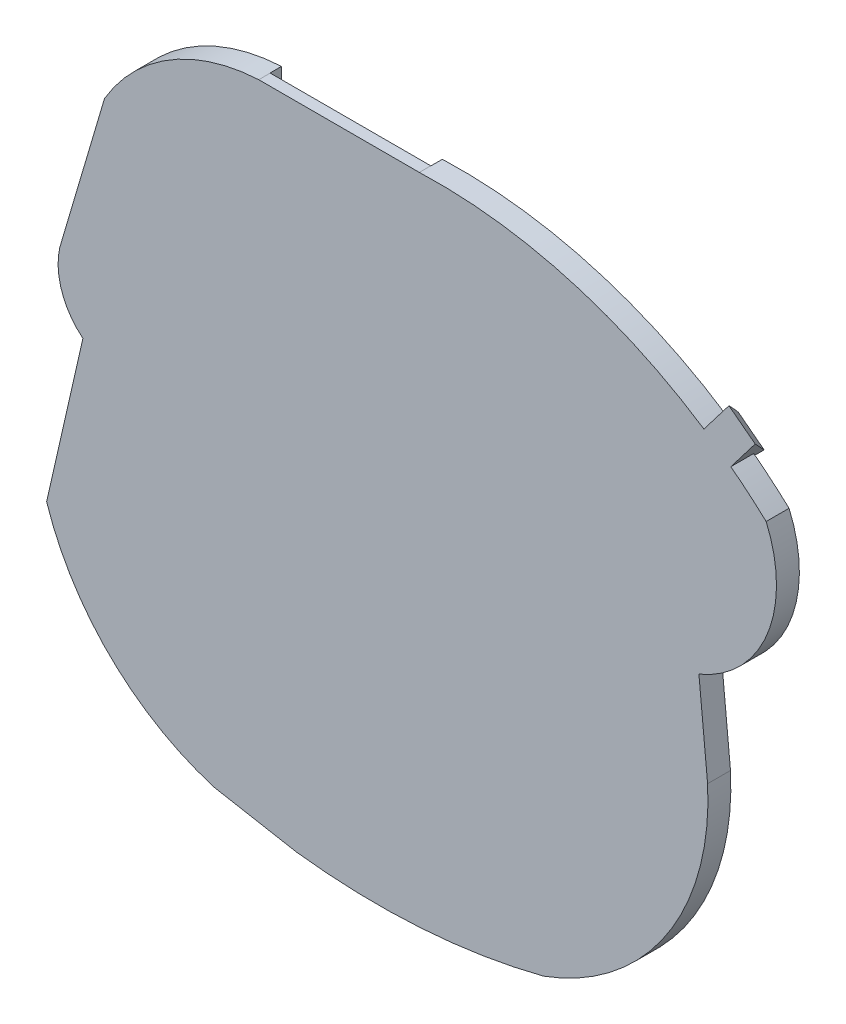
SolidWorks part; units mm, degrees
ref_plane "Front Plane" through (0, 0, 0) normal (0, 0, 1) x (1, 0, 0)
ref_plane "Top Plane" through (0, 0, 0) normal (0, 1, 0) x (1, 0, 0)
ref_plane "Right Plane" through (0, 0, 0) normal (1, 0, 0) x (0, 0, -1)
sketch "Sketch1" plane through (0, 0, 0) normal (0, 0, 1) x (1, 0, 0)
  line L0 (-85.5336, -305.9757) -> (-99.8837, -303.3682)
  line L2 (-13.742, -259.6992) -> (-15.2594, -243.8824)
  line L3 (-92.1446, -194.3927) -> (-64.0896, -194.3913)
  line L15 (-119.1233, -208.6879) -> (-126.5485, -233.818)
  line L20 (-129.2393, -274.7737) -> (-122.901, -246.8902)
  line L38 (-85.5336, -305.9757) -> (-85.5336, -305.9816)
  line L40 (-64.114, -192.3791) -> (-92.1689, -192.3791)
  line L44 (-64.0896, -194.3913) -> (-64.0896, -196.3927)
  line L45 (-19.5312, -241.5935) -> (-17.6923, -260.2487)
  line L46 (-125.176, -275.0633) -> (-119.3965, -249.6382)
  line L47 (-119.3965, -249.6382) -> (-118.0843, -245.1972)
  line L48 (-118.0843, -245.1972) -> (-118.3529, -245.047)
  line L49 (-122.5408, -235.0791) -> (-115.4629, -210.4053)
  line L50 (-92.1446, -196.3927) -> (-92.1446, -194.3927)
  line L51 (-92.1446, -194.3927) -> (-92.2026, -194.3927)
  line L52 (-117.3122, -209.5987) -> (-124.4351, -234.4295)
  line L53 (-120.4699, -246.2128) -> (-121.3326, -249.1327)
  line L54 (-121.3326, -249.1327) -> (-127.2648, -275.2293)
  line L55 (-15.6969, -260.1042) -> (-17.4155, -242.6686)
  line L63 (-92.1446, -194.3927) -> (-92.2026, -194.3927)
  line L64 (-117.3122, -209.5987) -> (-124.4351, -234.4295)
  line L65 (-120.4699, -246.2128) -> (-121.3326, -249.1327)
  line L66 (-121.3326, -249.1327) -> (-127.2648, -275.2293)
  line L67 (-15.6969, -260.1042) -> (-17.4155, -242.6686)
  arc A11 (-3.5093, -214.9046) -> (-15.2594, -243.8824) centre (-23.6253, -223.619) cw
  arc A12 (-64.114, -192.3791) -> (-3.5093, -214.9046) centre (-61.02, -276.8459) cw
  arc A13 (-119.1233, -208.6879) -> (-92.1689, -192.3791) centre (-90.4775, -225.6035) cw
  arc A14 (-122.901, -246.8902) -> (-126.5485, -233.818) centre (-115.4862, -237.7762) cw
  arc A15 (-13.742, -259.6992) -> (-42.3974, -303.1549) centre (-57.4462, -262.0557) cw
  arc A16 (-42.3974, -303.1549) -> (-85.5336, -305.9757) centre (-71.4399, -190.2643) cw
  arc A17 (-99.8837, -303.3682) -> (-129.2393, -274.7737) centre (-87.3068, -261.0907) cw
  arc A18 (-5.1894, -215.9632) -> (-64.0896, -194.3913) centre (-61.111, -277.4555) ccw
  arc A19 (-6.954, -217.065) -> (-64.0896, -196.3927) centre (-61.1117, -277.4561) ccw
  arc A20 (-43.5818, -299.408) -> (-17.6923, -260.2487) centre (-57.5026, -262.0667) ccw
  arc A21 (-98.4164, -299.6694) -> (-43.5818, -299.408) centre (-71.5229, -189.646) ccw
  arc A22 (-125.176, -275.0633) -> (-98.4164, -299.6694) centre (-85.5245, -258.7954) ccw
  arc A23 (-122.5408, -235.0791) -> (-118.3529, -245.047) centre (-115.4629, -237.9691) ccw
  arc A24 (-92.1446, -196.3927) -> (-115.4629, -210.4053) centre (-90.4142, -225.6804) ccw
  arc A25 (-92.2026, -194.3927) -> (-117.3122, -209.5987) centre (-90.4142, -225.6804) ccw
  arc A26 (-124.4351, -234.4295) -> (-120.4699, -246.2128) centre (-115.4629, -237.9691) ccw
  arc A27 (-127.2648, -275.2293) -> (-98.9548, -301.5967) centre (-85.5245, -258.7954) ccw
  arc A28 (-98.9548, -301.5967) -> (-42.9849, -301.3198) centre (-71.5229, -189.646) ccw
  arc A29 (-42.9849, -301.3198) -> (-15.6969, -260.1042) centre (-57.5026, -262.0667) ccw
  arc A30 (-5.1894, -215.9632) -> (-64.0896, -194.3913) centre (-61.111, -277.4555) ccw
  arc A37 (-92.2026, -194.3927) -> (-117.3122, -209.5987) centre (-90.4142, -225.6804) ccw
  arc A38 (-124.4351, -234.4295) -> (-120.4699, -246.2128) centre (-115.4629, -237.9691) ccw
  arc A39 (-127.2648, -275.2293) -> (-98.9548, -301.5967) centre (-85.5245, -258.7954) ccw
  arc A40 (-98.9548, -301.5967) -> (-42.9849, -301.3198) centre (-71.5229, -189.646) ccw
  arc A41 (-42.9849, -301.3198) -> (-15.6969, -260.1042) centre (-57.5026, -262.0667) ccw
  spline S3 degree 3 poles (-282.7446, 744.1526) (-190.4607, 422.5139) (-98.1767, 100.8752) (-5.8044, -221.0718) (-5.7146, -221.3797) (-5.5406, -221.9968) (-5.3948, -222.6207) (-5.3079, -223.259) (-5.2519, -223.9047) (-5.2394, -224.233) (-5.2497, -225.2081) (-5.3188, -225.8496) (-5.5066, -226.8003) (-5.5832, -227.1152) (-5.7634, -227.7415) (-5.8665, -228.0511) (-6.434, -229.563) (-7.0553, -230.6795) (-8.1541, -232.2617) (-8.5505, -232.7751) (-9.3836, -233.7652) (-9.8192, -234.241) (-11.173, -235.6207) (-12.1391, -236.4791) (-14.1549, -238.0987) (-15.1963, -238.8533) (-70.9415, -276.1696) (-191.3909, -204.5856) (324.8564, -1180.3097) knots -32.486215 -32.486215 -32.486215 -32.486215 0.125 0.125 0.15625 0.15625 0.1875 0.21875 0.21875 0.25 0.25 0.3125 0.3125 0.34375 0.34375 0.375 0.375 0.5 0.5 0.5625 0.5625 0.625 0.625 0.75 0.75 0.875 0.875 7.285103 7.285103 7.285103 7.285103 only from (-6.954, -217.065) to (-19.5312, -241.5935)
  spline S4 degree 3 poles (1790.212, -3800.1242) (-331.9971, -96.6547) (-94.8598, -297.861) (-13.4412, -240.0404) (-12.8926, -239.6332) (-11.8127, -238.7903) (-11.2804, -238.3537) (-9.727, -237.0047) (-8.7454, -236.0517) (-7.385, -234.5113) (-6.9487, -233.9768) (-6.1308, -232.8745) (-5.7503, -232.3084) (-4.7065, -230.5586) (-4.1387, -229.3247) (-3.5625, -227.3289) (-3.422, -226.6544) (-3.2527, -225.2963) (-3.2234, -224.611) (-3.2692, -223.5731) (-3.2996, -223.2276) (-3.3887, -222.5466) (-3.477, -222.0412) (-3.5963, -221.5435) (-3.6826, -221.2134) (-3.7302, -221.0494) (-371.9427, 1062.3721) (-740.1081, 2345.6295) (-1108.2736, 3628.8871) knots -8.964357 -8.964357 -8.964357 -8.964357 0.125 0.125 0.1875 0.1875 0.25 0.25 0.375 0.375 0.4375 0.4375 0.5 0.5 0.625 0.625 0.6875 0.6875 0.75 0.75 0.78125 0.78125 0.8125 0.828125 0.828125 0.84375 0.84375 123.052125 123.052125 123.052125 123.052125 only from (-17.4155, -242.6686) to (-5.1894, -215.9632)
  spline S6 degree 3 poles (-17.4155, -242.6686) (-16.2509, -241.9658) (-15.1093, -241.225) (-13.4412, -240.0404) (-12.8926, -239.6332) (-11.8127, -238.7903) (-11.2804, -238.3537) (-9.727, -237.0047) (-8.7454, -236.0517) (-7.385, -234.5113) (-6.9487, -233.9768) (-6.1308, -232.8745) (-5.7503, -232.3084) (-4.7065, -230.5586) (-4.1387, -229.3247) (-3.5625, -227.3289) (-3.422, -226.6544) (-3.2527, -225.2963) (-3.2234, -224.611) (-3.2692, -223.5731) (-3.2996, -223.2276) (-3.3887, -222.5466) (-3.477, -222.0412) (-3.5963, -221.5435) (-3.6826, -221.2134) (-3.7302, -221.0494) (-4.2479, -219.2446) (-4.7187, -217.6039) (-5.1894, -215.9632) knots 0 0 0 0 0.125 0.125 0.1875 0.1875 0.25 0.25 0.375 0.375 0.4375 0.4375 0.5 0.5 0.625 0.625 0.6875 0.6875 0.75 0.75 0.78125 0.78125 0.8125 0.828125 0.828125 0.84375 0.84375 1 1 1 1
  dimension "D1" = 0
extrude "Boss-Extrude1" add sketch "Sketch1" against normal blind 2 and the other way blind 2 contours A17 L0 A16 A15 L2 A11 A12 L40 A13 L15 A14 L20 S6 L67 A41 A40 A39 L66 L65 A38 L64 A37 L63 L3 A30 region at (-92.4105, -303.0308, 0) region at (-66.5159, -305.7575, 0) region at (-63.4279, -305.6212, 0) region at (-7.0475, -213.0787, 0)
sketch "Sketch4" plane through (0, 0, 2) normal (0, 0, 1) x (1, 0, 0)
  line L10 (-121.3326, -249.1327) -> (-127.2648, -275.2293) construction
  line L11 (-121.3326, -249.1327) -> (-127.2648, -275.2293)
  line L12 (-120.4699, -246.2128) -> (-121.3326, -249.1327) construction
  line L13 (-120.4699, -246.2128) -> (-121.3326, -249.1327)
  line L14 (-117.3122, -209.5987) -> (-124.4351, -234.4295) construction
  line L15 (-117.3122, -209.5987) -> (-124.4351, -234.4295)
  line L16 (-92.1446, -194.3927) -> (-64.0896, -194.3913) construction
  line L17 (-92.1446, -194.3927) -> (-64.0896, -194.3913)
  line L18 (-92.1446, -194.3927) -> (-92.2026, -194.3927) construction
  line L19 (-92.1446, -194.3927) -> (-92.2026, -194.3927)
  line L20 (-15.6969, -260.1042) -> (-17.4155, -242.6686) construction
  line L21 (-15.6969, -260.1042) -> (-17.4155, -242.6686)
  arc A7 (-42.9849, -301.3198) -> (-15.6969, -260.1042) centre (-57.5026, -262.0667) ccw construction
  arc A11 (-42.9849, -301.3198) -> (-15.6969, -260.1042) centre (-57.5026, -262.0667) ccw
  arc A12 (-98.9548, -301.5967) -> (-42.9849, -301.3198) centre (-71.5229, -189.646) ccw construction
  arc A13 (-98.9548, -301.5967) -> (-42.9849, -301.3198) centre (-71.5229, -189.646) ccw
  arc A14 (-127.2648, -275.2293) -> (-98.9548, -301.5967) centre (-85.5245, -258.7954) ccw construction
  arc A15 (-127.2648, -275.2293) -> (-98.9548, -301.5967) centre (-85.5245, -258.7954) ccw
  arc A16 (-124.4351, -234.4295) -> (-120.4699, -246.2128) centre (-115.4629, -237.9691) ccw construction
  arc A17 (-124.4351, -234.4295) -> (-120.4699, -246.2128) centre (-115.4629, -237.9691) ccw
  arc A18 (-92.2026, -194.3927) -> (-117.3122, -209.5987) centre (-90.4142, -225.6804) ccw construction
  arc A19 (-92.2026, -194.3927) -> (-117.3122, -209.5987) centre (-90.4142, -225.6804) ccw
  arc A20 (-5.1894, -215.9632) -> (-64.0896, -194.3913) centre (-61.111, -277.4555) ccw construction
  arc A21 (-5.1894, -215.9632) -> (-64.0896, -194.3913) centre (-61.111, -277.4555) ccw
  spline S1 degree 3 poles (1295.0144, -2931.4127) (-292.5014, -129.2405) (-87.9302, -292.9398) (-13.4412, -240.0404) (-12.8926, -239.6332) (-11.8127, -238.7903) (-11.2804, -238.3537) (-9.727, -237.0047) (-8.7454, -236.0517) (-7.385, -234.5113) (-6.9487, -233.9768) (-6.1308, -232.8745) (-5.7503, -232.3084) (-4.7065, -230.5586) (-4.1387, -229.3247) (-3.5625, -227.3289) (-3.422, -226.6544) (-3.2527, -225.2963) (-3.2234, -224.611) (-3.2692, -223.5731) (-3.2996, -223.2276) (-3.3887, -222.5466) (-3.477, -222.0412) (-3.5963, -221.5435) (-3.6826, -221.2134) (-3.7302, -221.0494) (-280.02, 741.9714) (-556.2628, 1704.8281) (-832.5055, 2667.6849) knots -8.185436 -8.185436 -8.185436 -8.185436 0.125 0.125 0.1875 0.1875 0.25 0.25 0.375 0.375 0.4375 0.4375 0.5 0.5 0.625 0.625 0.6875 0.6875 0.75 0.75 0.78125 0.78125 0.8125 0.828125 0.828125 0.84375 0.84375 92.539425 92.539425 92.539425 92.539425 only from (-17.4155, -242.6686) to (-5.1894, -215.9632) construction
  spline S2 degree 3 poles (-17.4155, -242.6686) (-16.2509, -241.9658) (-15.1093, -241.225) (-13.4412, -240.0404) (-12.8926, -239.6332) (-11.8127, -238.7903) (-11.2804, -238.3537) (-9.727, -237.0047) (-8.7454, -236.0517) (-7.385, -234.5113) (-6.9487, -233.9768) (-6.1308, -232.8745) (-5.7503, -232.3084) (-4.7065, -230.5586) (-4.1387, -229.3247) (-3.5625, -227.3289) (-3.422, -226.6544) (-3.2527, -225.2963) (-3.2234, -224.611) (-3.2692, -223.5731) (-3.2996, -223.2276) (-3.3887, -222.5466) (-3.477, -222.0412) (-3.5963, -221.5435) (-3.6826, -221.2134) (-3.7302, -221.0494) (-4.2479, -219.2446) (-4.7187, -217.6039) (-5.1894, -215.9632) knots 0 0 0 0 0.125 0.125 0.1875 0.1875 0.25 0.25 0.375 0.375 0.4375 0.4375 0.5 0.5 0.625 0.625 0.6875 0.6875 0.75 0.75 0.78125 0.78125 0.8125 0.828125 0.828125 0.84375 0.84375 1 1 1 1
extrude "Boss-Extrude2" add sketch "Sketch4" against normal blind 2
sketch "Sketch5" plane through (0.0091, -194.3883, 0) normal (0, -1, 0) x (1, 0, 0)
  line L6 (-92.1537, 0) -> (-92.2118, 0)
  line L7 (-92.2118, 0) -> (-92.2118, -2)
  line L8 (-92.2118, -2) -> (-92.1537, -2)
  line L9 (-92.1537, -2) -> (-64.0988, -2)
  line L10 (-64.0988, -2) -> (-64.0988, 0)
  line L11 (-64.0988, 0) -> (-92.1537, 0)
  line L12 (-92.1537, 0) -> (-92.2118, 0)
  line L13 (-92.2118, 0) -> (-92.2118, -2)
  line L14 (-92.2118, -2) -> (-92.1537, -2)
  line L15 (-92.1537, -2) -> (-64.0988, -2)
  line L16 (-64.0988, -2) -> (-64.0988, 0)
  line L17 (-64.0988, 0) -> (-92.1537, 0)
  dimension "D1" = 0
extrude "Cut-Extrude2" cut sketch "Sketch5" against normal blind 3
sketch "Sketch6" plane through (0, 0, -2) normal (0, 0, -1) x (-1, 0, 0)
  line L0 (10.8623, -211.2468) -> (9.6803, -209.701)
  line L1 (15.4617, -207.9957) -> (14.3826, -206.3536)
  line L2 (14.3826, -206.3536) -> (9.6803, -209.701)
  line L13 (64.0896, -194.3913) -> (64.0897, -192.3782)
  line L14 (15.2594, -243.8824) -> (13.742, -259.6992)
  line L15 (85.5336, -305.9757) -> (99.8837, -303.3682)
  line L16 (129.2393, -274.7737) -> (122.901, -246.8902)
  line L17 (126.5485, -233.818) -> (119.1233, -208.6879)
  line L18 (92.2027, -192.3808) -> (92.2026, -194.3927)
  line L19 (117.3122, -209.5987) -> (124.4351, -234.4295)
  line L20 (120.4699, -246.2128) -> (121.3326, -249.1327)
  line L21 (121.3326, -249.1327) -> (127.2648, -275.2293)
  line L22 (15.6969, -260.1042) -> (17.4155, -242.6686)
  arc A0 (64.0896, -194.3913) -> (5.1894, -215.9632) centre (61.111, -277.4555) ccw construction
  arc A1 (64.0897, -192.3782) -> (3.5093, -214.9046) centre (61.02, -276.8459) ccw construction
  arc A15 (64.0896, -194.3913) -> (5.1894, -215.9632) centre (61.111, -277.4555) ccw
  arc A16 (64.0897, -192.3782) -> (3.5093, -214.9046) centre (61.02, -276.8459) ccw
  arc A17 (3.5093, -214.9046) -> (15.2594, -243.8824) centre (23.6253, -223.619) ccw
  arc A18 (13.742, -259.6992) -> (42.3974, -303.1549) centre (57.4462, -262.0557) ccw
  arc A19 (42.3974, -303.1549) -> (85.5336, -305.9757) centre (71.4399, -190.2643) ccw
  arc A20 (99.8837, -303.3682) -> (129.2393, -274.7737) centre (87.3068, -261.0907) ccw
  arc A21 (122.901, -246.8902) -> (126.5485, -233.818) centre (115.4862, -237.7762) ccw
  arc A22 (119.1233, -208.6879) -> (92.2027, -192.3808) centre (90.4775, -225.6035) ccw
  arc A23 (117.3122, -209.5987) -> (92.2026, -194.3927) centre (90.4142, -225.6804) ccw
  arc A24 (120.4699, -246.2128) -> (124.4351, -234.4295) centre (115.4629, -237.9691) ccw
  arc A25 (98.9548, -301.5967) -> (127.2648, -275.2293) centre (85.5245, -258.7954) ccw
  arc A26 (42.9849, -301.3198) -> (98.9548, -301.5967) centre (71.5229, -189.646) ccw
  arc A27 (15.6969, -260.1042) -> (42.9849, -301.3198) centre (57.5026, -262.0667) ccw
  arc A28 (15.4617, -207.9957) -> (10.8623, -211.2468) centre (61.111, -277.4555) ccw
  spline S1 degree 3 poles (-328.0239, -1181.107) (186.222, -205.1616) (66.7964, -277.9313) (13.4412, -240.0404) (12.8926, -239.6332) (11.8127, -238.7903) (11.2804, -238.3537) (9.727, -237.0047) (8.7454, -236.0517) (7.385, -234.5113) (6.9487, -233.9768) (6.1308, -232.8745) (5.7503, -232.3084) (4.7065, -230.5586) (4.1387, -229.3247) (3.5625, -227.3289) (3.422, -226.6544) (3.2527, -225.2963) (3.2234, -224.611) (3.2692, -223.5731) (3.2996, -223.2276) (3.3887, -222.5466) (3.477, -222.0412) (3.5963, -221.5435) (3.6826, -221.2134) (3.7302, -221.0494) (96.1725, 101.1627) (188.5679, 423.2107) (280.9632, 745.2588) knots -5.809886 -5.809886 -5.809886 -5.809886 0.125 0.125 0.1875 0.1875 0.25 0.25 0.375 0.375 0.4375 0.4375 0.5 0.5 0.625 0.625 0.6875 0.6875 0.75 0.75 0.78125 0.78125 0.8125 0.828125 0.828125 0.84375 0.84375 31.513332 31.513332 31.513332 31.513332 only from (17.4155, -242.6686) to (5.1894, -215.9632)
  dimension "D1" = 0
extrude "Boss-Extrude3" add sketch "Sketch6" along normal blind 3 and the other way blind 4
sketch "Sketch7" plane through (95.0754, -72.6957, 0) normal (0.7944, -0.6074, 0) x (0, 0, -1)
  line L3 (-2, -172.4651) -> (5, -172.4651)
  line L4 (-2, -165.4651) -> (-2, -172.4651)
  arc A1 (5, -172.4651) -> (-2, -165.4651) centre (-2, -172.4651) ccw
extrude "Boss-Extrude4" add sketch "Sketch7" against normal up to vertex (5.7686 mm away) separate body up to point (-14.3826, -206.3536, -2)
sketch "Sketch8" plane through (0, 0, -5) normal (0, 0, -1) x (-1, 0, 0)
  line L0 (14.2629, -206.1971) -> (14.3826, -206.3536)
  line L1 (14.3826, -206.3536) -> (9.6803, -209.701)
  line L2 (9.6803, -209.701) -> (14.2629, -206.1971)
extrude "Boss-Extrude5" add sketch "Sketch8" against normal up to surface (7 mm away) up to face at (-75.5388, -248.6579, 2)
sketch "Sketch9" plane through (95.0754, -72.6957, 0) normal (0.7944, -0.6074, 0) x (0, 0, -1)
  line L0 (-2, -165.4651) -> (5, -174.411)
  line L3 (-2, -165.4651) -> (7.2164, -165.4651)
  line L4 (7.2164, -165.4651) -> (7.2164, -174.411)
  line L5 (7.2164, -174.411) -> (5, -174.411)
extrude "Cut-Extrude3" cut sketch "Sketch9" against normal up to vertex (5.7686 mm away) up to point (-14.2629, -206.1971, -5)
